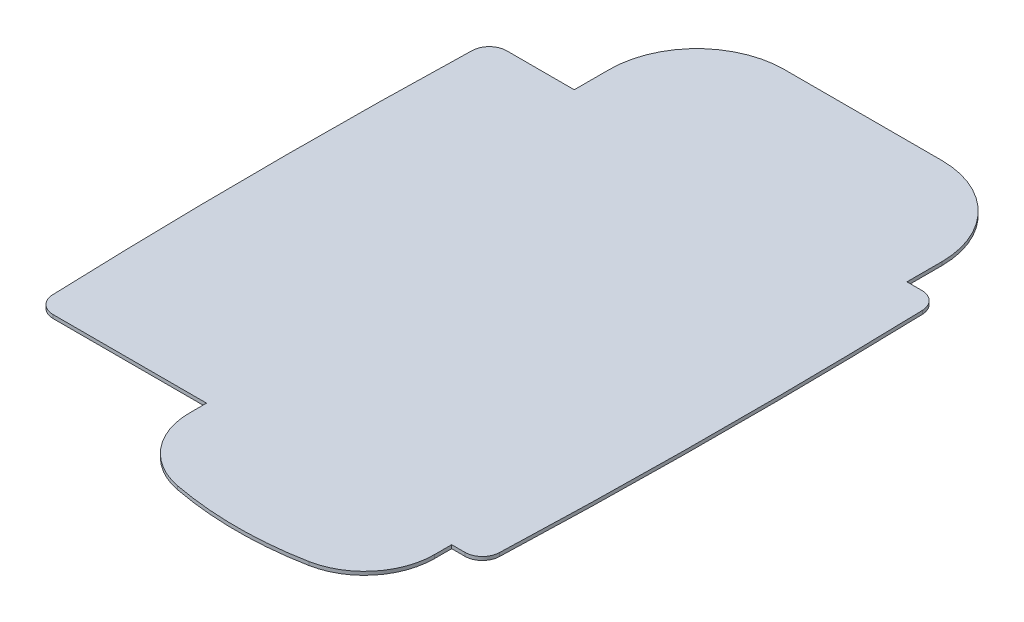
SolidWorks part; units mm, degrees
ref_plane "正面" through (0, 0, 0) normal (0, 0, 1) x (1, 0, 0)
ref_plane "平面" through (0, 0, 0) normal (0, 1, 0) x (1, 0, 0)
ref_plane "右側面" through (0, 0, 0) normal (1, 0, 0) x (0, 0, -1)
sketch "ｽｹｯﾁ1" plane through (0, 0, 0) normal (0, 1, 0) x (1, 0, 0)
  line L1 (-65, 92.5) -> (65, 92.5)
  line L2 (-65, 92.5) -> (-65, -92.5) construction
  line L3 (-65, -92.5) -> (65, -92.5)
  line L4 (65, 92.5) -> (65, -92.5) construction
  ellipse E0 centre (0, 0) end of major axis (0, -350) minor radius 65
  point P11 (-65, 0)
  dimension "D1" = 130
  dimension "D2" = 700
  dimension "D3" = 185
extrude "ﾎﾞｽ - 押し出し1" add sketch "ｽｹｯﾁ1" along normal mid plane 1 contours L3 E0 L1 region at (0, 0, 0)
sketch "ｽｹｯﾁ3" plane through (0, 0.5, 0) normal (0, 1, 0) x (1, 0, 0)
  line L0 (-62.6889, 92.5) -> (62.6889, 92.5) construction
  line L1 (-65, 92.5) -> (-40, 92.5)
  line L2 (-65, 92.5) -> (-65, 57.5)
  line L3 (-65, 57.5) -> (-40, 57.5)
  line L4 (-40, 92.5) -> (-40, 57.5)
  ellipse E0 centre (0, 0) end of major axis (0, -350) minor radius 65 (-62.6889, 92.5) -> (-62.6889, -92.5) ccw construction
  dimension "D1" = 35
  dimension "D2" = 25
extrude "ｶｯﾄ - 押し出し1" cut sketch "ｽｹｯﾁ3" against normal through all
sketch "ｽｹｯﾁ4" plane through (0, 0.5, 0) normal (0, 1, 0) x (1, 0, 0)
  line L0 (-40, 92.5) -> (62.6889, 92.5) construction
  line L1 (55, 92.5) -> (65, 92.5)
  line L2 (55, 92.5) -> (55, 57.5)
  line L3 (55, 57.5) -> (65, 57.5)
  line L4 (65, 92.5) -> (65, 57.5)
  line L5 (-64.1168, 57.5) -> (-40, 57.5) construction
  ellipse E0 centre (0, 0) end of major axis (0, -350) minor radius 65 (62.6889, -92.5) -> (62.6889, 92.5) ccw construction
  dimension "D1" = 10
extrude "ｶｯﾄ - 押し出し2" cut sketch "ｽｹｯﾁ4" against normal through all
sketch "ｽｹｯﾁ5" plane through (0, 0.5, 0) normal (0, 1, 0) x (1, 0, 0)
  line L0 (-62.6889, -92.5) -> (62.6889, -92.5) construction
  line L1 (-65, -72.5) -> (-15, -72.5)
  line L2 (-65, -72.5) -> (-65, -92.5)
  line L3 (-65, -92.5) -> (-15, -92.5)
  line L4 (-15, -72.5) -> (-15, -92.5)
  ellipse E0 centre (0, 0) end of major axis (0, -350) minor radius 65 (-64.1168, 57.5) -> (-62.6889, -92.5) ccw construction
  point P11 (0, 0)
  dimension "D1" = 20
  dimension "D2" = 50
extrude "ｶｯﾄ - 押し出し3" cut sketch "ｽｹｯﾁ5" against normal through all
sketch "ｽｹｯﾁ6" plane through (0, 0.5, 0) normal (0, 1, 0) x (1, 0, 0)
  line L0 (-15, -92.5) -> (62.6889, -92.5) construction
  line L1 (55, -72.5) -> (65, -72.5)
  line L2 (55, -72.5) -> (55, -92.5)
  line L3 (55, -92.5) -> (65, -92.5)
  line L4 (65, -72.5) -> (65, -92.5)
  line L7 (-15, -72.5) -> (-63.5902, -72.5) construction
  line L8 (55, 92.5) -> (55, 57.5) construction
  ellipse E0 centre (0, 0) end of major axis (0, -350) minor radius 65 (62.6889, -92.5) -> (64.1168, 57.5) ccw construction
extrude "ｶｯﾄ - 押し出し4" cut sketch "ｽｹｯﾁ6" against normal through all
sketch "ｽｹｯﾁ7" plane through (0, 0, 0) normal (0, 1, 0) x (1, 0, 0)
  line L0 (-15, -92.5) -> (55, -92.5) construction
  line L1 (-15, -92.5) -> (55, -92.5)
  arc A0 (-15, -92.5) -> (55, -92.5) centre (20, 1.175) ccw
  dimension "D1" = 100
extrude "ﾎﾞｽ - 押し出し2" add sketch "ｽｹｯﾁ7" along normal mid plane 1
sketch "ｽｹｯﾁ8" plane through (0, 0.5, 0) normal (0, 1, 0) x (1, 0, 0)
  line L0 (-40, 92.5) -> (55, 92.5) construction
  line L1 (-40, 57.5) -> (-40, 92.5) construction
  line L2 (55, 92.5) -> (55, 57.5) construction
  line L3 (55, 92.5) -> (55, 57.5)
  line L4 (-40, 92.5) -> (55, 92.5)
  line L5 (-40, 57.5) -> (-40, 92.5)
  circle A0 centre (-15, 67.5) radius 25
  circle A1 centre (30, 67.5) radius 25
  line M6 (55, 92.5) -> (-40, 92.5)
  line M7 (-40, 92.5) -> (-40, 57.5)
  dimension "D1" = 45
extrude "ｶｯﾄ - 押し出し5" cut sketch "ｽｹｯﾁ8" against normal through all contours A0 L4 M7 | A1 L3 M6 region at (49.4158, 0.5, -86.9158) region at (-34.4158, 0.5, -86.9158)
sketch "ｽｹｯﾁ9" plane through (0, 0, 0) normal (0, 1, 0) x (1, 0, 0)
  line L0 (-64.1168, 57.5) -> (-40, 57.5) construction
  line L1 (-65, 57.5) -> (-20, 57.5)
  line L2 (-65, 57.5) -> (-65, 5.5)
  line L3 (-65, 5.5) -> (-20, 5.5)
  line L4 (-20, 57.5) -> (-20, 5.5)
  arc A0 (-15, 92.5) -> (-40, 67.5) centre (-15, 67.5) ccw construction
  arc A1 (-15, 92.5) -> (-40, 67.5) centre (-15, 67.5) ccw
  circle A2 centre (-15, 67.5) radius 20
  ellipse E0 centre (0, 0) end of major axis (0, -350) minor radius 65 (-64.1168, 57.5) -> (-63.5902, -72.5) ccw construction
  point P15 (0, 0)
  point P16 (0, 0)
  dimension "D1" = 40
  dimension "D2" = 52
  dimension "D3" = 45
fillet "ﾌｨﾚｯﾄ1" radius 5 4 edges at (-64.1168, 0, -57.5) (-63.5902, 0, 72.5) (63.5902, 0, 72.5) (64.1168, 0, -57.5)
fillet "ﾌｨﾚｯﾄ2" radius 20 2 edges at (-15, 0, 92.5) (55, 0, 92.5)
